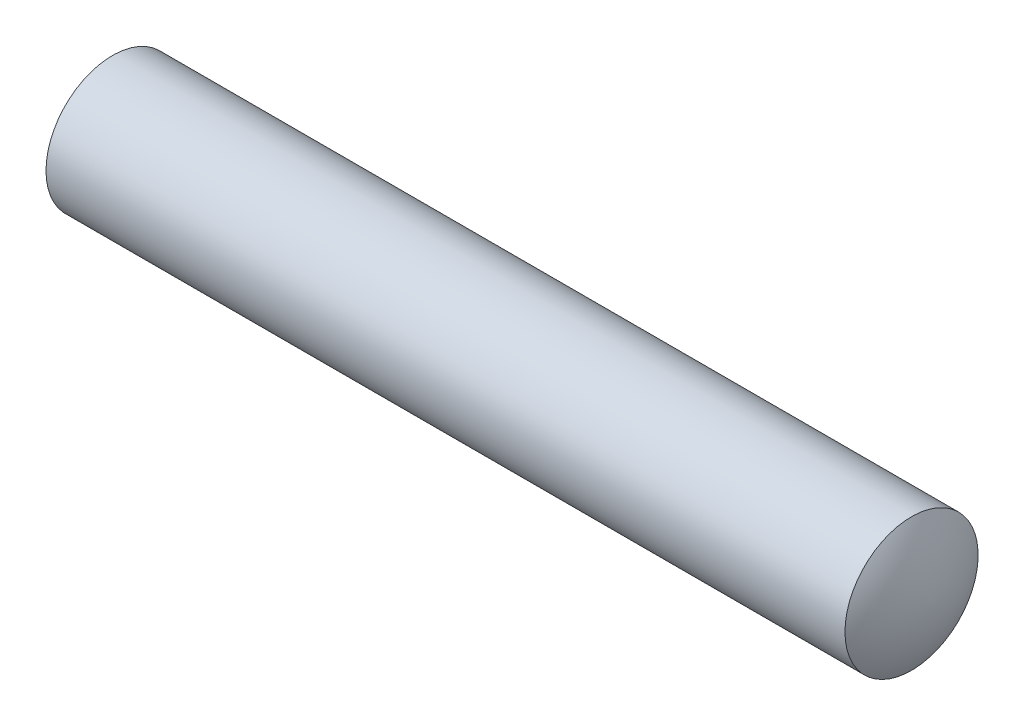
SolidWorks part; units mm, degrees
ref_plane "Спереди" through (0, 0, 0) normal (0, 0, 1) x (1, 0, 0)
ref_plane "Сверху" through (0, 0, 0) normal (0, 1, 0) x (1, 0, 0)
ref_plane "Справа" through (0, 0, 0) normal (1, 0, 0) x (0, 0, -1)
sketch "Эскиз1" plane through (0, 0, 0) normal (0, 0, 1) x (1, 0, 0)
  line L0 (0, 0) -> (14.3069, 0) construction
  line L1 (0, 0) -> (0, 6.3046) construction
  line L3 (0, 2.5) -> (30, 2.5)
  line L6 (30, 2.5) -> (30, -0.4836) construction
  line L7 (-0.75, 0) -> (30.75, 0)
  arc A1 (0, 2.5) -> (-0.75, 0) centre (4.2481, -0.1369) ccw
  arc A2 (30, 2.5) -> (30.75, 0) centre (25.7519, -0.1369) cw
  point P7 (0, 0)
  point P10 (0, 0)
  dimension "D1" = 0.75
  dimension "D4" = 5
  dimension "D6" = 5
  dimension "D2" = 5
  dimension "D3" = 30
  dimension "D5" = 0.75
revolve "Повернуть2" add sketch "Эскиз1" angle 360 about L0
